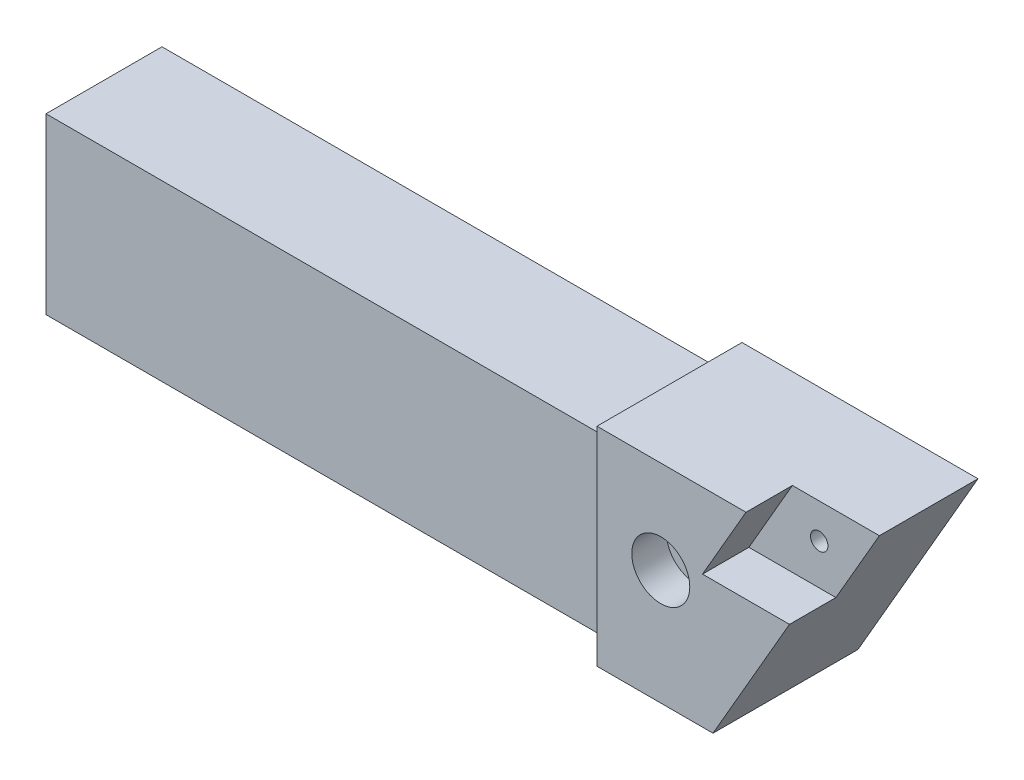
SolidWorks part; units mm, degrees
ref_plane "前视基准面" through (0, 0, 0) normal (0, 0, 1) x (1, 0, 0)
ref_plane "上视基准面" through (0, 0, 0) normal (0, 1, 0) x (1, 0, 0)
ref_plane "右视基准面" through (0, 0, 0) normal (1, 0, 0) x (0, 0, -1)
sketch "草图1" plane through (0, 0, 0) normal (0, 0, 1) x (1, 0, 0)
  line L1 (-50, 15) -> (50, 15)
  line L2 (-50, 15) -> (-50, -15)
  line L3 (-50, -15) -> (50, -15)
  line L4 (50, 15) -> (50, -15)
  line L5 (-50, 15) -> (50, -15) construction
  line L6 (-50, -15) -> (50, 15) construction
  point P0 (0, 0)
  dimension "D1" = 100
  dimension "D2" = 30
extrude "凸台-拉伸1" add sketch "草图1" along normal blind 20
sketch "草图2" plane through (0, 0, 20) normal (0, 0, 1) x (1, 0, 0)
  line L0 (50, -15) -> (70, -15)
  line L1 (70, -15) -> (90.6951, 20.845)
  line L2 (90.6951, 20.845) -> (50, 20.845)
  line L3 (50, 20.845) -> (50, -15)
  dimension "D1" = 60
  dimension "D2" = 20
extrude "凸台-拉伸2" add sketch "草图2" along normal blind 5 and the other way blind 20
fillet "圆角1" radius 5 2 edges
sketch "草图3" plane through (0, 0, 25) normal (0, 0, 1) x (1, 0, 0)
  line L0 (90.6951, 20.845) -> (57.2845, 1.5554) construction
  line L1 (90.6951, 20.845) -> (50, 20.845) construction
  line L3 (75.6951, 20.845) -> (68.1951, 7.8547)
  line L4 (68.1951, 7.8547) -> (83.1951, 7.8547)
  line L5 (70, -15) -> (90.6951, 20.845) construction
  line L6 (75.6951, 20.845) -> (90.6951, 20.845)
  line L7 (90.6951, 20.845) -> (83.1951, 7.8547)
  dimension "D1" = 30
  dimension "D2" = 15
  dimension "D3" = 15
extrude "切除-拉伸1" cut sketch "草图3" against normal blind 8
sketch "草图4" plane through (0, 0, 17) normal (0, 0, 1) x (1, 0, 0)
  line L0 (90.6951, 20.845) -> (68.1951, 7.8547) construction
  circle A0 centre (80.3195, 14.8547) radius 1.5
  dimension "D1" = 3
  dimension "D2" = 14
extrude "切除-拉伸2" cut sketch "草图4" against normal through all
cosmetic thread "装饰螺纹线1" parameters "D2"=9
hole_wizard "孔1" positions "3D草图1" profile "草图6" legacy
sketch3d "3D草图1"
  line L0 (50, 20, 25) -> (50, -15, 25) construction
  line L1 (75.6951, 20.845, 25) -> (50, 20.845, 25) construction
  point P0 (61, 4.845, 25)
  dimension "D1" = 11
  dimension "D2" = 16
sketch "草图6" plane through (61, 4.845, 25) normal (1, 0, 0) x (0, -1, 0)
  line L0 (0, 0) -> (0, 25)
  line L1 (0, 25) -> (2.5, 25)
  line L2 (2.5, 25) -> (2.5, 6)
  line L3 (2.5, 6) -> (5, 6)
  line L4 (5, 6) -> (5, 0)
  line L5 (5, 0) -> (0, 0)
  line L6 (0, 110) -> (0, -10) construction
  dimension "直径" = 5
  dimension "深度" = 25
  dimension "柱坑直径" = 10
  dimension "柱坑深度" = 6
cosmetic thread "装饰螺纹线2" parameters "D2"=24
